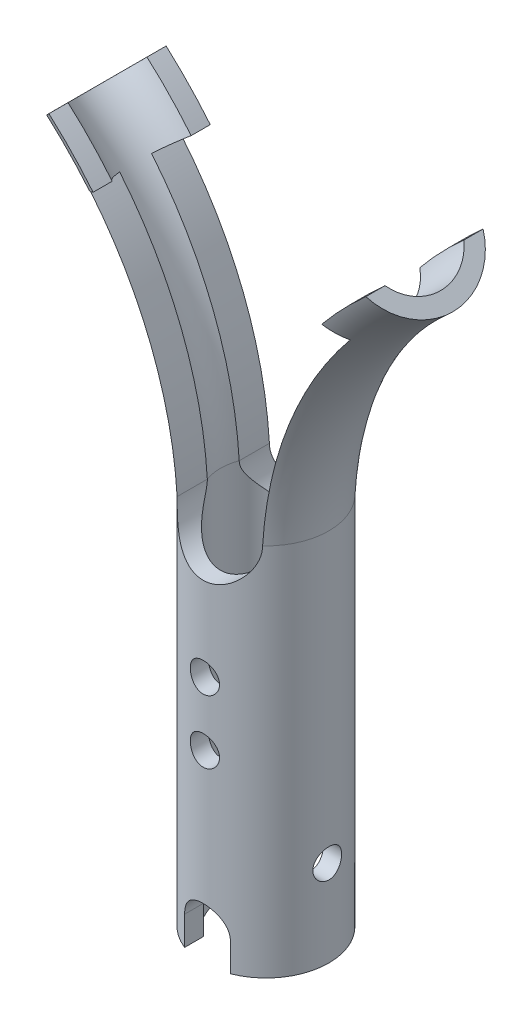
SolidWorks part; units mm, degrees
ref_plane "Front Plane" through (0, 0, 0) normal (0, 0, 1) x (1, 0, 0)
ref_plane "Top Plane" through (0, 0, 0) normal (0, 1, 0) x (1, 0, 0)
ref_plane "Right Plane" through (0, 0, 0) normal (1, 0, 0) x (0, 0, -1)
ref_axis "Axis1" through (0, -0.5891, 0) along (0, 1, 0)
sketch "Sketch1" plane through (0, 0, 0) normal (0, 1, 0) x (1, 0, 0)
  circle A0 centre (0, 0) radius 1.0922
  dimension "D1" = 2.1844
extrude "Extrude-Thin1" add sketch "Sketch1" along normal blind 6.5 thin thin type one direction reverse wall 0.3
sketch "Sketch2" plane through (0, 6.5, 0) normal (0, 1, 0) x (1, 0, 0)
  arc A0 (-0.5732, -0.9297) -> (-0.2666, 1.0592) centre (0, 0) cw
  circle A1 centre (0, 0) radius 1.0922 construction
  arc A2 (-0.3687, -0.7011) -> (-0.1565, 0.7766) centre (0, 0) cw
  circle A3 centre (0, 0) radius 0.7922 construction
sketch "Sketch3" plane through (0, 6.5, 0) normal (0, 1, 0) x (1, 0, 0)
  line L0 (-0.7422, -0.277) -> (-0.7422, -0.8013)
  line L1 (-0.7422, 0.8013) -> (-0.7422, 0.277)
  line L2 (0, 0) -> (-1.0922, 0) construction
  arc A0 (-0.7422, -0.8013) -> (-0.7422, 0.8013) centre (0, 0) cw
  circle A1 centre (0, 0) radius 1.0922 construction
  arc A2 (-0.7422, -0.277) -> (-0.7422, 0.277) centre (0, 0) cw
  circle A5 centre (0, 0) radius 0.7922 construction
  arc A6 (-0.1565, 0.7766) -> (-0.3687, -0.7011) centre (0, 0) ccw construction
  dimension "D1" = 0.35
sketch "Sketch4" plane through (0, 0, 0) normal (0, 0, 1) x (1, 0, 0)
  arc A0 (-1.0922, 6.5) -> (-3.2448, 10.8715) centre (-7.4522, 6.084) ccw
  dimension "D1" = 6.3736
  dimension "D2" = 5
sweep "Sweep1" [suppressed] add profiles "Sketch3" path "Sketch4"
sketch "Sketch12" plane through (0, 6.5, 0) normal (0, 1, 0) x (1, 0, 0)
  line L0 (-0.3969, -1.0175) -> (-0.3969, -0.6856)
  line L1 (-0.3969, 0.6856) -> (-0.3969, 1.0175)
  circle A0 centre (0, 0) radius 1.0922 construction
  arc A1 (-0.3969, 1.0175) -> (-0.3969, -1.0175) centre (0, 0) ccw
  circle A2 centre (0, 0) radius 0.7922 construction
  arc A3 (-0.3969, 0.6856) -> (-0.3969, -0.6856) centre (0, 0) ccw
  dimension "D1" = 0.3969
sweep "Sweep2" add profiles "Sketch12" path "Sketch4<2>"
sketch "Sketch4<2>" plane through (0, 0, 0) normal (0, 0, 1) x (1, 0, 0) same geometry as "Sketch4"
sketch "Sketch13" plane through (0, 0, 0) normal (0, 0, 1) x (1, 0, 0)
  arc A0 (-1.0922, 6.5) -> (-3.2448, 10.8715) centre (-7.4522, 6.084) ccw construction
  arc A1 (-1.0922, 6.5) -> (-3.2448, 10.8715) centre (-7.4522, 6.084) ccw construction
  arc A2 (-1.0922, 6.5) -> (-2.5484, 10.1553) centre (-7.4522, 6.084) ccw
  dimension "D1" = 4
sketch "Sketch14" plane through (0, 6.5, 0) normal (0, 1, 0) x (1, 0, 0)
  line L2 (-0.3969, -1.0175) -> (-0.3969, -0.6856)
  line L3 (-0.3969, 0.6856) -> (-0.3969, 1.0175)
  line L4 (-0.3969, -1.0175) -> (-0.3969, -0.6856)
  line L5 (-0.3969, 0.6856) -> (-0.3969, 1.0175)
  line L6 (-0.7422, -0.8013) -> (-0.7422, -0.277)
  line L7 (-0.7422, 0.277) -> (-0.7422, 0.8013)
  line L8 (-0.7422, -0.8013) -> (-0.7422, -0.277)
  line L9 (-0.7422, 0.277) -> (-0.7422, 0.8013)
  arc A0 (-0.7422, -0.277) -> (-0.3969, -0.6856) centre (0, 0) ccw
  arc A1 (-0.7422, -0.8013) -> (-0.3969, -1.0175) centre (0, 0) ccw
  arc A2 (-0.3969, 0.6856) -> (-0.3969, -0.6856) centre (0, 0) ccw
  arc A3 (-0.3969, 1.0175) -> (-0.3969, -1.0175) centre (0, 0) ccw
  arc A4 (-0.3969, 0.6856) -> (-0.7422, 0.277) centre (0, 0) ccw
  arc A5 (-0.3969, 1.0175) -> (-0.7422, 0.8013) centre (0, 0) ccw
  arc A6 (-0.7422, 0.8013) -> (-0.7422, -0.8013) centre (0, 0) ccw
  arc A7 (-0.7422, 0.277) -> (-0.7422, -0.277) centre (0, 0) ccw
  dimension "D1" = 0
  dimension "D2" = 0
sweep "Cut-Sweep1" cut profiles "Sketch14" path "Sketch13"
mirror "Mirror1" about plane through (0, 0, 0) normal (1, 0, 0) of "Sweep2", "Cut-Sweep1"
sketch "Sketch5" plane through (0, 0, 0) normal (0, 0, 1) x (1, 0, 0)
  line L1 (0.7422, 6.5) -> (-0.7422, 6.5) construction
  line L2 (0.7422, 6.5) -> (-0.7422, 6.5) construction
  circle A0 centre (0, 6.5) radius 0.7422
extrude "Cut-Extrude1" cut sketch "Sketch5" against normal through all both and the other way through all
sketch "Sketch6" plane through (0, 0, 0) normal (0, 0, 1) x (1, 0, 0)
  line L0 (1.0922, 0) -> (1.0922, 6.5) construction
  line L1 (1.0922, 4.7578) -> (-0.5078, 4.7578)
  line L2 (1.0922, 4.7578) -> (1.0922, 3.9578)
  line L3 (1.0922, 3.9578) -> (-0.5078, 3.9578)
  line L4 (-0.5078, 4.7578) -> (-0.5078, 3.9578)
  arc A1 (-0.7422, 6.5) -> (0.7422, 6.5) centre (0, 6.5) ccw construction
  point P6 (0, 5.7578)
  dimension "D1" = 1
  dimension "D2" = 1.6
  dimension "D3" = 0.8
extrude "Cut-Extrude2" [suppressed] cut sketch "Sketch6" against normal through all both and the other way through all
pattern_linear "LPattern1" [suppressed] count 4 spacing 1.2 of bodies 106
sketch "Sketch7" plane through (0, 0, 0) normal (0, 0, 1) x (1, 0, 0)
  line L0 (-3.9437, 25.3767) -> (-2.6955, 24.3236)
  line L1 (-2.6955, 24.3236) -> (-3.0029, 23.9592)
  line L2 (-3.0029, 23.9592) -> (-4.2334, 24.9973)
  line L3 (-4.2334, 24.9973) -> (-3.9437, 25.3767)
extrude "Cut-Extrude3" [suppressed] cut sketch "Sketch7" against normal blind 1 and the other way blind 1
mirror "Mirror2" [suppressed] about plane through (0, 0, 0) normal (1, 0, 0)
sketch "Sketch10" plane through (0, 0, 0) normal (0, 0, 1) x (1, 0, 0)
  line L0 (0.7422, 6.5) -> (1.0922, 6.5) construction
  line L1 (0.3983, 0.5) -> (0.3983, 0)
  line L2 (0.3983, 0) -> (-0.3954, 0)
  line L3 (-0.3954, 0) -> (-0.3954, 0.5)
  line L4 (-1.0922, 0) -> (1.0922, 0) construction
  line L5 (-1.0922, 0) -> (1.0922, 0) construction
  circle A0 centre (0.0014, 4.3) radius 0.254
  circle A1 centre (0.0014, 0.5) radius 0.3969 construction
  arc A2 (0.3983, 0.5) -> (-0.3954, 0.5) centre (0.0014, 0.5) ccw
  circle A3 centre (0.0014, 3.2) radius 0.254
  dimension "D1" = 0.508
  dimension "D3" = 0.7937
  dimension "D5" = 0.508
  dimension "D2" = 0.5
  dimension "D4" = 2.2
  dimension "D6" = 1.1
extrude "Cut-Extrude5" cut sketch "Sketch10" against normal blind 10 and the other way blind 10
sketch "Sketch9" plane through (0, 0, 0) normal (1, 0, 0) x (0, 0, -1)
  line L0 (-1.0922, 0) -> (1.0922, 0) construction
  line L1 (-1.0922, 0) -> (1.0922, 0) construction
  line L2 (0, 0) -> (0, 1.5) construction
  circle A0 centre (0, 1.5) radius 0.25
  dimension "D1" = 0.5
  dimension "D2" = 1.5
extrude "Cut-Extrude4" cut sketch "Sketch9" against normal blind 10 and the other way blind 10
sketch "Sketch15" plane through (0, 0, 0) normal (0, -1, 0) x (1, 0, 0)
  circle A0 centre (0, 0) radius 0.9922
  arc A1 (0.3983, -1.017) -> (0.3983, 1.017) centre (0, 0) ccw construction
  circle A2 centre (0, 0) radius 1.3141
  dimension "D1" = 0.1
extrude "Cut-Extrude6" [suppressed] cut sketch "Sketch15" against normal blind 2
equation "\"pin_hole_position\"=1.5"
equation "\"D2@Sketch9\"=\"pin_hole_position\""
